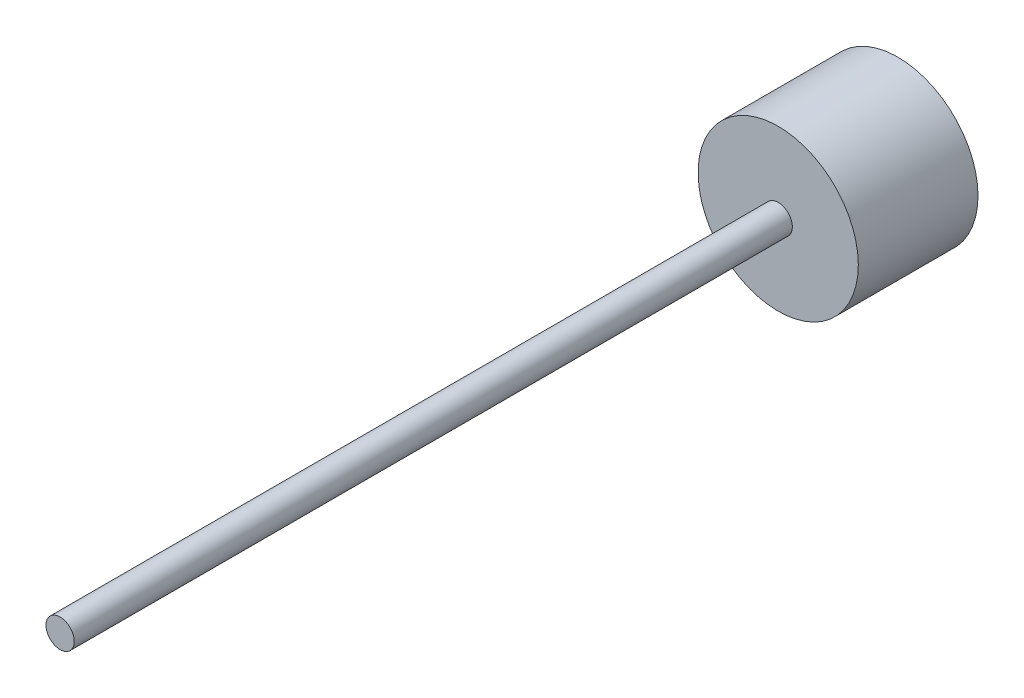
SolidWorks part; units mm, degrees
material "1023 Carbon Steel Sheet (SS)"
ref_plane "Front Plane" through (0, 0, 0) normal (0, 0, 1) x (1, 0, 0)
ref_plane "Top Plane" through (0, 0, 0) normal (0, 1, 0) x (1, 0, 0)
ref_plane "Right Plane" through (0, 0, 0) normal (1, 0, 0) x (0, 0, -1)
sketch "Sketch1" plane through (0, 0, 0) normal (0, 0, 1) x (1, 0, 0)
  circle A0 centre (0, 0) radius 8.5
  circle A1 centre (0, 0) radius 1.5
  dimension "D1" = 17
  dimension "D2" = 3
sketch "Sketch7" plane through (0, 0, 0) normal (0, 0, 1) x (1, 0, 0)
extrude "Boss-Extrude1" add sketch "Sketch1" along normal blind 12.7
extrude "Boss-Extrude2" add sketch "Sketch1<5>" along normal blind 88.9 contours A1
sketch "Sketch1<5>" plane through (0, 0, 0) normal (0, 0, 1) x (1, 0, 0) same geometry as "Sketch1"
